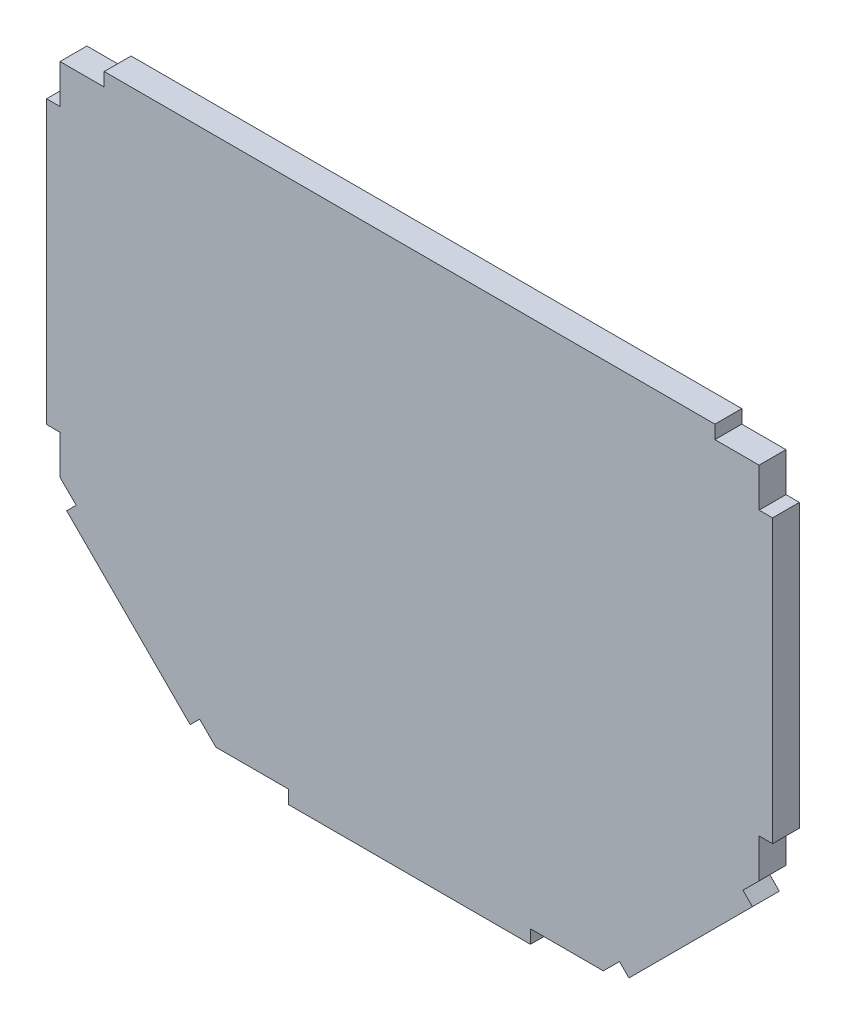
SolidWorks part; units mm, degrees
ref_plane "Front Plane" through (0, 0, 0) normal (0, 0, 1) x (1, 0, 0)
ref_plane "Top Plane" through (0, 0, 0) normal (0, 1, 0) x (1, 0, 0)
ref_plane "Right Plane" through (0, 0, 0) normal (1, 0, 0) x (0, 0, -1)
sketch "Sketch2" plane through (0, 0, 0) normal (0, 0, 1) x (1, 0, 0)
  line L0 (0, 0) -> (34.417, 0)
  line L1 (183.134, 0) -> (190.7672, 7.6332)
  line L2 (256.7721, 73.6381) -> (256.7721, 92.0531)
  line L3 (256.7721, 243.8181) -> (235.8905, 243.8181)
  line L4 (-73.6381, 243.8181) -> (-73.6381, 225.4031)
  line L5 (-73.6381, 73.6381) -> (-66.0049, 66.0049)
  line L6 (195.2573, 3.1431) -> (253.629, 61.5148)
  line L7 (34.417, -6.35) -> (148.717, -6.35)
  line L8 (34.417, -6.35) -> (34.417, 0)
  line L10 (148.717, -6.35) -> (148.717, 0)
  line L11 (-52.7565, 243.8181) -> (-73.6381, 243.8181)
  line L13 (195.2573, 3.1431) -> (190.7672, 7.6332)
  line L14 (253.629, 61.5148) -> (249.1389, 66.0049)
  line L15 (256.7721, 225.4031) -> (256.7721, 243.8181)
  line L16 (263.1221, 225.4031) -> (256.7721, 225.4031)
  line L17 (263.1221, 225.4031) -> (263.1221, 92.0531)
  line L18 (263.1221, 92.0531) -> (256.7721, 92.0531)
  line L20 (249.1389, 66.0049) -> (256.7721, 73.6381)
  line L21 (-7.6332, 7.6332) -> (0, 0)
  line L22 (148.717, 0) -> (183.134, 0)
  line L23 (-79.9881, 225.4031) -> (-73.6381, 225.4031)
  line L24 (-79.9881, 225.4031) -> (-79.9881, 92.0531)
  line L25 (-79.9881, 92.0531) -> (-73.6381, 92.0531)
  line L26 (-70.495, 61.5148) -> (-66.0049, 66.0049)
  line L27 (-12.1233, 3.1431) -> (-7.6332, 7.6332)
  line L28 (-12.1233, 3.1431) -> (-70.495, 61.5148)
  line L29 (-73.6381, 92.0531) -> (-73.6381, 73.6381)
  line L30 (-52.7565, 243.8181) -> (-52.7565, 250.1681)
  line L31 (-52.7565, 250.1681) -> (235.8905, 250.1681)
  line L32 (235.8905, 243.8181) -> (235.8905, 250.1681)
  point P3 (0, 0)
  dimension "D1" = 135
  dimension "D2" = 183.134
  dimension "D3" = 170.18
  dimension "D4" = 104.14
  dimension "D5" = 6.35
  dimension "D6" = 114.3
  dimension "D7" = 34.417
  dimension "D8" = 6.35
  dimension "D9" = 82.55
  dimension "D10" = 10.795
  dimension "D11" = 6.35
  dimension "D12" = 133.35
  dimension "D13" = 18.415
extrude "Boss-Extrude1" add sketch "Sketch2" along normal blind 12.7
